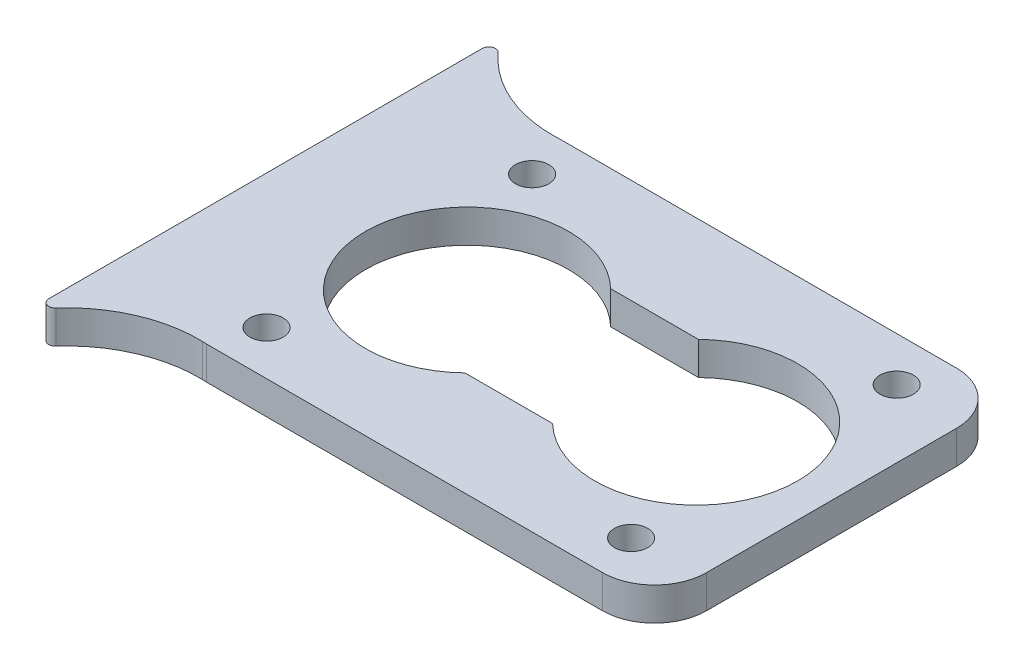
SolidWorks part; units mm, degrees
material "AISI 4130 Steel, annealed at 865C"
ref_plane "X-Y Datum" through (0, 0, 0) normal (0, 0, 1) x (1, 0, 0)
ref_plane "X-Z Datum" through (0, 0, 0) normal (0, 1, 0) x (1, 0, 0)
ref_plane "Y-Z Datum" through (0, 0, 0) normal (1, 0, 0) x (0, 0, -1)
sketch "Sketch1" plane through (0, 0, 0) normal (0, 1, 0) x (1, 0, 0)
  line L0 (-157.7346, 34.7035) -> (-119.7346, 34.7035)
  line L1 (-162.7346, 63.7035) -> (-162.7346, 39.7035)
  line L2 (-119.7346, 68.7035) -> (-157.7346, 68.7035)
  line L3 (-114.7346, 39.7035) -> (-114.7346, 63.7035)
  line L4 (-134.5216, 44.7035) -> (-142.9477, 44.7035)
  line L5 (-142.9477, 58.7035) -> (-134.5216, 58.7035)
  arc A0 (-119.7346, 34.7035) -> (-114.7346, 39.7035) centre (-119.7346, 39.7035) ccw
  arc A1 (-162.7346, 39.7035) -> (-157.7346, 34.7035) centre (-157.7346, 39.7035) ccw
  arc A2 (-157.7346, 68.7035) -> (-162.7346, 63.7035) centre (-157.7346, 63.7035) ccw
  arc A3 (-114.7346, 63.7035) -> (-119.7346, 68.7035) centre (-119.7346, 63.7035) ccw
  arc A4 (-134.5216, 44.7035) -> (-127.7346, 41.9535) centre (-127.7346, 51.7035) ccw
  arc A5 (-149.7346, 41.9535) -> (-142.9477, 44.7035) centre (-149.7346, 51.7035) ccw
  arc A6 (-149.7346, 61.4535) -> (-149.7346, 41.9535) centre (-149.7346, 51.7035) ccw
  arc A7 (-142.9477, 58.7035) -> (-149.7346, 61.4535) centre (-149.7346, 51.7035) ccw
  arc A8 (-127.7346, 61.4535) -> (-134.5216, 58.7035) centre (-127.7346, 51.7035) ccw
  arc A9 (-127.7346, 41.9535) -> (-127.7346, 61.4535) centre (-127.7346, 51.7035) ccw
  arc A10 (-121.2346, 37.3535) -> (-121.2346, 40.5535) centre (-121.2346, 38.9535) ccw
  arc A11 (-121.2346, 40.5535) -> (-121.2346, 37.3535) centre (-121.2346, 38.9535) ccw
  arc A12 (-156.2346, 37.3535) -> (-156.2346, 40.5535) centre (-156.2346, 38.9535) ccw
  arc A13 (-156.2346, 40.5535) -> (-156.2346, 37.3535) centre (-156.2346, 38.9535) ccw
  arc A14 (-156.2346, 62.8535) -> (-156.2346, 66.0535) centre (-156.2346, 64.4535) ccw
  arc A15 (-156.2346, 66.0535) -> (-156.2346, 62.8535) centre (-156.2346, 64.4535) ccw
  arc A16 (-121.2346, 62.8535) -> (-121.2346, 66.0535) centre (-121.2346, 64.4535) ccw
  arc A17 (-121.2346, 66.0535) -> (-121.2346, 62.8535) centre (-121.2346, 64.4535) ccw
  point P43 (0, 0)
  point P44 (-121.2346, 66.0535)
  point P45 (-143.3391, 44.8482)
  point P47 (-121.238, 63.1663)
  dimension "D4" = 1.6
  dimension "D5" = 9.75
  dimension "D6" = 9.75
  dimension "D8" = 9.75
  dimension "D9" = 9.75
  dimension "D12" = 5
  dimension "D15" = 5
  dimension "D18" = 38
  dimension "D34" = 3.2
  dimension "D1" = 22
  dimension "D2" = 6.5
  dimension "D3" = 28.5
  dimension "D7" = 14
  dimension "D10" = 8.4261
  dimension "D11" = 6.7869
  dimension "D13" = 8
  dimension "D14" = 38
  dimension "D16" = 24
  dimension "D17" = 24
  dimension "D19" = 51.7035
  dimension "D20" = 149.7346
  dimension "D21" = 7
  dimension "D22" = 9.75
  dimension "D23" = 7
  dimension "D24" = 6.7869
  dimension "D25" = 19.5
  dimension "D26" = 19.5
  dimension "D27" = 6.7869
  dimension "D28" = 14
  dimension "D29" = 16.75
  dimension "D30" = 12.75
  dimension "D31" = 12.75
  dimension "D32" = 12.75
  dimension "D33" = 12.75
  dimension "D35" = 6.5
extrude "Boss-Extrude1" add sketch "Sketch1" along normal blind 3.175
sketch "Sketch2" plane through (0, 0, 0) normal (0, -1, 0) x (1, 0, 0)
  line L2 (-162.7346, -51.7035) -> (-114.7346, -51.7035) construction
  line L6 (-162.7346, -63.7035) -> (-162.7346, -39.7035) construction
  line L9 (-119.7346, -68.7035) -> (-157.7346, -68.7035) construction
  line L10 (-119.7346, -68.7035) -> (-157.7346, -68.7035)
  line L11 (-114.7346, -39.7035) -> (-114.7346, -63.7035) construction
  line L12 (-169.0846, -74.3821) -> (-169.0846, -29.0249)
  line L13 (-162.7346, -63.7035) -> (-162.7346, -39.7035)
  arc A6 (-169.0846, -74.3821) -> (-157.7346, -68.7035) centre (-158.4873, -81.3812) cw
  arc A7 (-162.7346, -63.7035) -> (-157.7346, -68.7035) centre (-157.7346, -63.7035) ccw construction
  arc A8 (-162.7346, -63.7035) -> (-157.7346, -68.7035) centre (-157.7346, -63.7035) ccw
  arc A9 (-162.7346, -39.7035) -> (-157.7346, -34.7035) centre (-157.7346, -39.7035) cw
  arc A10 (-169.0846, -29.0249) -> (-157.7346, -34.7035) centre (-158.4873, -22.0258) ccw
  point P19 (-169.0846, -51.7035)
  arc M7 (-162.7346, -63.7035) -> (-157.7346, -68.7035) centre (-157.7346, -63.7035) ccw
  line M8 (-157.7346, -68.7035) -> (-119.7346, -68.7035)
  arc M9 (-119.7346, -68.7035) -> (-114.7346, -63.7035) centre (-119.7346, -63.7035) ccw
  dimension "D1" = 12.7
  dimension "D2" = 6.35
  dimension "D3" = 22.6786
extrude "Boss-Extrude2" add sketch "Sketch2" against normal blind 3.175 contours L10 M9 | M8 M7 region at (-165.8282, 0, -51.7035)
fillet "Fillet1" radius 0.635 2 edges at (-169.0846, 1.5875, -29.0249) (-169.0846, 1.5875, -74.3821)
